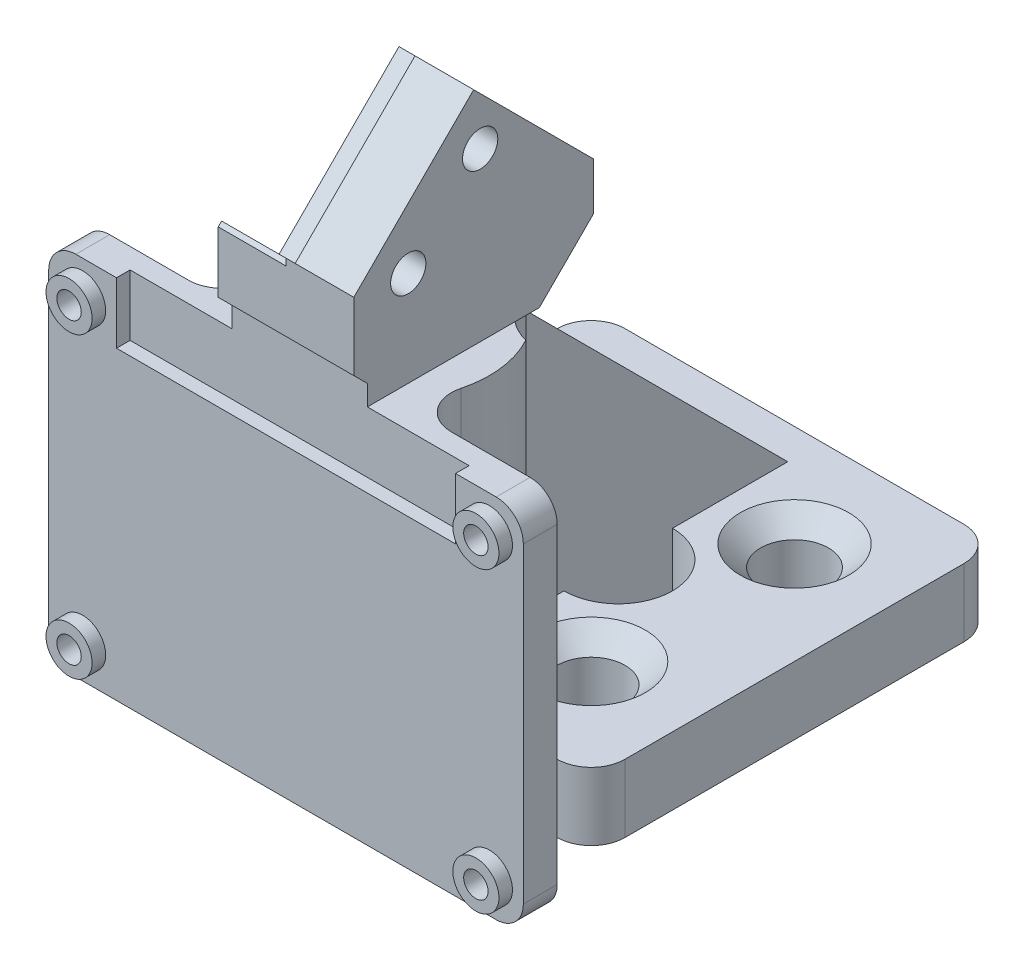
SolidWorks part; units mm, degrees
ref_plane "Front Plane" through (0, 0, 0) normal (0, 0, 1) x (1, 0, 0)
ref_plane "Top Plane" through (0, 0, 0) normal (0, 1, 0) x (1, 0, 0)
ref_plane "Right Plane" through (0, 0, 0) normal (1, 0, 0) x (0, 0, -1)
sketch "Sketch1" plane through (0, 0, 0) normal (0, 1, 0) x (1, 0, 0)
  circle A0 centre (0, 0) radius 15
  dimension "D1" = 30
extrude "Boss-Extrude1" add sketch "Sketch1" along normal blind 54
sketch "Sketch2" plane through (0, 0, 0) normal (1, 0, 0) x (0, 0, -1)
  line L0 (15, 54) -> (-15, 54) construction
  line L1 (-15, 54) -> (20.3553, 54)
  line L2 (-15, 54) -> (-15, 69)
  line L4 (20.3553, 54) -> (20.3553, 69)
  line L5 (-15, 69) -> (2.6777, 86.6777)
  line L6 (2.6777, 86.6777) -> (20.3553, 69)
  point P6 (0, 100)
  dimension "D1" = 25
  dimension "D2" = 15
  dimension "D3" = 15
  dimension "D4" = 45
  dimension "D5" = 15
extrude "Boss-Extrude2" add sketch "Sketch2" along normal mid plane 20
sketch "Sketch4" plane through (0, 42, 42) normal (0, 0.7071, 0.7071) x (1, 0, 0)
  line L0 (10, 38.1838) -> (-10, 38.1838) construction
  line L1 (-12.7, 38.1838) -> (0, 38.1838)
  line L2 (-12.7, 38.1838) -> (-12.7, 63.1838)
  line L3 (-12.7, 63.1838) -> (0, 63.1838)
  line L4 (0, 38.1838) -> (0, 63.1838)
  line L5 (10, 63.1838) -> (-10, 63.1838) construction
  dimension "D1" = 12.7
extrude "Cut-Extrude2" cut sketch "Sketch4" against normal blind 12.7
chamfer "Chamfer1" distance 1 angle 45 1 edges at (-5, 69, 15) first distance on face at (0, 61.5, 15)
sketch "Sketch5" plane through (0, 0, 0) normal (0, -1, 0) x (1, 0, 0)
  circle A0 centre (0, 0) radius 75
  dimension "D1" = 150
sketch "Sketch6" plane through (10, 0, 0) normal (1, 0, 0) x (0, 0, -1)
  line L0 (2.6777, 86.6777) -> (-15, 69) construction
  line L1 (20.3553, 69) -> (2.6777, 86.6777) construction
  line L2 (3.6323, 78.652) -> (-6.9743, 68.0454) construction
  circle A0 centre (3.6323, 78.652) radius 2.6
  circle A1 centre (-6.9743, 68.0454) radius 2.6
  dimension "D4" = 5.2
  dimension "D1" = 6.35
  dimension "D2" = 15
  dimension "D3" = 5
extrude "Cut-Extrude3" cut sketch "Sketch6" against normal through all
sketch "Sketch7" plane through (0, 0, 15) normal (0, 0, 1) x (1, 0, 0)
  line L0 (-31, 0) -> (31, 0)
  line L1 (-35, 4) -> (-35, 50)
  line L2 (-31, 54) -> (31, 54)
  line L3 (35, 4) -> (35, 50)
  line L4 (10, 54) -> (0, 54) construction
  circle A0 centre (-30, 49) radius 1.8
  circle A1 centre (30, 49) radius 1.8
  circle A2 centre (30, 5) radius 1.8
  circle A3 centre (-30, 5) radius 1.8
  arc A4 (31, 54) -> (35, 50) centre (31, 50) cw
  arc A5 (31, 0) -> (35, 4) centre (31, 4) ccw
  arc A6 (-31, 0) -> (-35, 4) centre (-31, 4) cw
  arc A7 (-35, 50) -> (-31, 54) centre (-31, 50) cw
  circle A8 centre (0, 27) radius 5 construction
  point P4 (30, 5)
  point P5 (30, 49)
  point P6 (-30, 49)
  point P7 (-30, 5)
  dimension "D1" = 3.6
  dimension "D2" = 10
  dimension "D3" = 4
  dimension "D4" = 65
  dimension "D5" = 30
  dimension "D6" = 30
  dimension "D7" = 5
  dimension "D8" = 49
  dimension "D9" = 22
  dimension "D10" = 22
  dimension "D11" = 5
extrude "Boss-Extrude4" add sketch "Sketch7" against normal blind 5
fillet "Fillet1" radius 5 2 edges at (-11.1803, 27, 10) (11.1803, 27, 10)
sketch "Sketch8" plane through (0, 0, 0) normal (0, -1, 0) x (1, 0, 0)
  line L1 (30, 0) -> (-30, 0)
  line L2 (30, 0) -> (30, -60)
  line L3 (30, -60) -> (-30, -60)
  line L4 (-30, 0) -> (-30, -60)
  point P4 (0, 0)
  dimension "D1" = 60
  dimension "D2" = 60
extrude "Boss-Extrude5" add sketch "Sketch8" against normal blind 10
sketch "Sketch9" plane through (0, 0, 0) normal (1, 0, 0) x (0, 0, -1)
  line L0 (15, 50) -> (55, 10)
  line L1 (15, 10) -> (15, 54) construction
  line L2 (60, 10) -> (0, 10) construction
  line L3 (15, 50) -> (10, 50)
  line L4 (10, 50) -> (10, 10)
  line L5 (10, 10) -> (55, 10)
  dimension "D1" = 45
  dimension "D2" = 5
  dimension "D3" = 40
extrude "Boss-Extrude6" add sketch "Sketch9" along normal mid plane 8
fillet "Fillet2" radius 5 4 edges at (-30, 5, -60) (30, 5, -60) (-30, 5, 0) (30, 5, 0)
sketch "Sketch10" plane through (0, 10, 0) normal (0, 1, 0) x (1, 0, 0)
  line L0 (-25, 60) -> (25, 60) construction
  line L1 (-15, 45) -> (15, 45) construction
  line L2 (-15, 45) -> (-15, 15) construction
  line L3 (-15, 15) -> (15, 15) construction
  line L4 (15, 45) -> (15, 15) construction
  line L5 (-15, 45) -> (15, 15) construction
  line L6 (-15, 15) -> (15, 45) construction
  circle A0 centre (15, 45) radius 5
  circle A1 centre (-15, 45) radius 5
  circle A2 centre (-15, 15) radius 5
  circle A3 centre (15, 15) radius 5
  point P8 (0, 30)
  dimension "D1" = 10
  dimension "D2" = 30
  dimension "D3" = 30
  dimension "D4" = 30
extrude "Cut-Extrude4" cut sketch "Sketch10" against normal through all
chamfer "Chamfer2" distance 8 angle 45 1 edges at (0, 54, -20.3553)
sketch "Sketch11" plane through (0, 0, 15) normal (0, 0, 1) x (1, 0, 0)
  circle A0 centre (-30, 49) radius 1.8
  circle A1 centre (30, 49) radius 1.8
  circle A2 centre (30, 5) radius 1.8
  circle A3 centre (-30, 5) radius 1.8
  circle A4 centre (-30, 49) radius 1.8 construction
extrude "Extrude-Thin1" add sketch "Sketch11" along normal blind 2 thin thin type one direction wall 1.6
sketch "Sketch12" plane through (0, 0, 15) normal (0, 0, 1) x (1, 0, 0)
  line L0 (-10, 54) -> (-31, 54) construction
  line L1 (-25, 59) -> (25, 59)
  line L2 (-25, 59) -> (-25, 45)
  line L3 (-25, 45) -> (25, 45)
  line L4 (25, 59) -> (25, 45)
  line L5 (-35, 50) -> (-35, 4) construction
  line L6 (35, 4) -> (35, 50) construction
  dimension "D1" = 9
  dimension "D2" = 10
  dimension "D3" = 10
  dimension "D4" = 14
extrude "Cut-Extrude5" cut sketch "Sketch12" against normal blind 2
chamfer "Chamfer3" distance 2 angle 45 1 edges at (0, 59, 13)
sketch "Sketch13" plane through (0, 0, 10) normal (0, 0, -1) x (-1, 0, 0)
  line L649 (-30, 45.8823) -> (-27.3, 47.4412)
  line L650 (-27.3, 47.4412) -> (-27.3, 50.5588)
  line L651 (-27.3, 50.5588) -> (-30, 52.1177)
  line L652 (-30, 52.1177) -> (-32.7, 50.5588)
  line L653 (-32.7, 50.5588) -> (-32.7, 47.4412)
  line L654 (-32.7, 47.4412) -> (-30, 45.8823)
  line L655 (30, 45.8823) -> (32.7, 47.4412)
  line L656 (32.7, 47.4412) -> (32.7, 50.5588)
  line L657 (32.7, 50.5588) -> (30, 52.1177)
  line L658 (30, 52.1177) -> (27.3, 50.5588)
  line L659 (27.3, 50.5588) -> (27.3, 47.4412)
  line L660 (27.3, 47.4412) -> (30, 45.8823)
  line L662 (27.3, 6.5588) -> (27.3, 3.4412)
  line L663 (27.3, 3.4412) -> (30, 1.8823)
  line L664 (30, 1.8823) -> (32.7, 3.4412)
  line L665 (32.7, 3.4412) -> (32.7, 6.5588)
  line L666 (32.7, 6.5588) -> (30, 8.1177)
  line L667 (30, 8.1177) -> (27.3, 6.5588)
  line L668 (-32.7, 6.5588) -> (-32.7, 3.4412)
  line L669 (-32.7, 3.4412) -> (-30, 1.8823)
  line L670 (-30, 1.8823) -> (-27.3, 3.4412)
  line L671 (-27.3, 3.4412) -> (-27.3, 6.5588)
  line L672 (-27.3, 6.5588) -> (-30, 8.1177)
  line L673 (-30, 8.1177) -> (-32.7, 6.5588)
  circle A0 centre (-30, 49) radius 2.7 construction
  circle A1 centre (30, 49) radius 2.7 construction
  circle A2 centre (30, 5) radius 2.7 construction
  circle A3 centre (-30, 5) radius 2.7 construction
  circle A4 centre (-30, 49) radius 1.8 construction
  circle A5 centre (30, 49) radius 1.8 construction
  circle A8 centre (-30, 5) radius 1.8 construction
  circle A9 centre (30, 5) radius 1.8 construction
  dimension "D1" = 5.4
  dimension "D2" = 5.4
  dimension "D3" = 5.4
  dimension "D4" = 5.4
extrude "Cut-Extrude6" cut sketch "Sketch13" against normal blind 2
sketch "Sketch14" plane through (0, 10, 0) normal (0, 1, 0) x (1, 0, 0)
  circle A0 centre (15, 15) radius 8
  circle A1 centre (-15, 15) radius 8
  circle A2 centre (15, 15) radius 5 construction
  dimension "D1" = 16
extrude "Cut-Extrude7" cut sketch "Sketch14" along normal up to surface (44 mm away) up to face at (20.8063, 54, 8.6403)
chamfer "Chamfer4" distance 3 angle 45 4 edges at (-15, 10, -40) (15, 10, -40) (15, 10, -10) (-15, 10, -10)
sketch "Sketch15" plane through (0, 10, 0) normal (0, 1, 0) x (1, 0, 0)
  line L0 (4, 14.4568) -> (4, 55) construction
  line L1 (4, 22) -> (4, 38)
  line L2 (-25, 60) -> (25, 60) construction
  arc A0 (4, 22) -> (4, 38) centre (4, 30) ccw
  dimension "D1" = 8
  dimension "D2" = 30
extrude "Cut-Extrude8" cut sketch "Sketch15" against normal through all
sketch "Sketch16" [suppressed] plane through (0, 42, 42) normal (0, 0.7071, 0.7071) x (1, 0, 0)
  line L1 (10, 63.1838) -> (-10, 63.1838)
  line L2 (10, 63.1838) -> (10, 31.1838)
  line L3 (10, 31.1838) -> (-10, 31.1838)
  line L4 (-10, 63.1838) -> (-10, 31.1838)
  dimension "D1" = 32
extrude "Cut-Extrude9" [suppressed] cut sketch "Sketch16" against normal blind 5.8
sketch "Sketch17" [suppressed] plane through (-10, 0, 0) normal (-1, 0, 0) x (0, 0, 1)
  line L0 (5.4332, 70.3643) -> (0.5542, 65.4853)
  line L1 (10.8988, 64.8988) -> (-6.7789, 82.5765) construction
  line L2 (-11.6579, 77.6974) -> (6.0197, 60.0197) construction
  line L3 (0.5542, 65.4853) -> (9.0395, 57)
  line L4 (9.0395, 57) -> (13, 57)
  line L5 (5.4332, 70.3643) -> (15.8988, 59.8988)
  line L6 (15.8988, 59.8988) -> (13, 57)
  dimension "D1" = 12
extrude "Cut-Extrude10" [suppressed] cut sketch "Sketch17" against normal through all
sketch "Sketch18" [suppressed] plane through (0, 33.0197, 33.0197) normal (0, 0.7071, 0.7071) x (1, 0, 0)
  line L0 (-6.35, 53.1838) -> (-6.35, 63.1838) construction
  line L1 (10, 63.1838) -> (6.7267, 63.1838)
  line L2 (10, 63.1838) -> (10, 53.1838)
  line L3 (10, 53.1838) -> (6.7267, 53.1838)
  line L4 (-22.7, 63.1838) -> (-22.7, 53.1838)
  line L5 (-19.4267, 53.1838) -> (-22.7, 53.1838)
  line L6 (-19.4267, 63.1838) -> (-22.7, 63.1838)
  line L7 (6.7267, 53.1838) -> (-19.4267, 53.1838) construction
  arc A4 (6.7267, 63.1838) -> (-19.4267, 63.1838) centre (-6.35, 58.1838) ccw
  arc A5 (6.7267, 53.1838) -> (-19.4267, 53.1838) centre (-6.35, 58.1838) cw
  point P8 (10, 58.1838)
  point P12 (-6.35, 63.1838)
  point P15 (-6.35, 53.1838)
  dimension "D3" = 14
  dimension "D1" = 5
  dimension "D2" = 32.7
extrude "Boss-Extrude7" [suppressed] add sketch "Sketch18" along normal up to surface (6.9 mm away) up to face at (5, 77.8388, 6.1612)
sketch "Sketch19" [suppressed] plane through (0, 20.8223, 20.8223) normal (0, -0.7071, -0.7071) x (1, 0, 0)
  line L0 (10, -46.9203) -> (10, -58.234) construction
  line L1 (-22.7, -63.1838) -> (-22.7, -53.1838) construction
  line L2 (6.25, -55.1838) -> (10, -55.1838)
  line L3 (3.25, -58.1838) -> (3.25, -63.1838)
  line L4 (6.7267, -63.1838) -> (-10, -63.1838) construction
  line L5 (10, -55.1838) -> (10, -63.1838)
  line L6 (10, -63.1838) -> (3.25, -63.1838)
  arc A0 (6.25, -55.1838) -> (3.25, -58.1838) centre (6.25, -58.1838) ccw
  point P4 (-22.7, -58.1838)
  dimension "D2" = 3
  dimension "D1" = 3.75
extrude "Cut-Extrude11" [suppressed] cut sketch "Sketch19" against normal up to surface (17.2497 mm away) up to face at (-5, 68.8586, -2.8191)
sketch "Sketch20" [suppressed] plane through (0, 33.0197, 33.0197) normal (0, -0.7071, -0.7071) x (1, 0, 0)
  line L0 (6.25, -58.1838) -> (-18.95, -58.1838) construction
  line L1 (-22.7, -63.1838) -> (-22.7, -53.1838) construction
  line L2 (10, -55.1838) -> (10, -63.1838) construction
  circle A0 centre (6.25, -58.1838) radius 1.5
  circle A1 centre (-18.95, -58.1838) radius 1.5
  point P5 (-22.7, -58.1838)
  dimension "D3" = 3
  dimension "D1" = 3.75
  dimension "D2" = 3.75
extrude "Cut-Extrude12" [suppressed] cut sketch "Sketch20" against normal through all
chamfer "Chamfer5" [suppressed] distance 7 angle 45
sketch "Sketch21" [suppressed] plane through (0, 0, 0) normal (0, 0, 1) x (1, 0, 0)
  line L0 (-10, 54) -> (-15, 54)
  line L1 (-15, 54) -> (-23.25, 62.25)
  line L2 (-23.25, 62.25) -> (-23.25, 75.5054)
  line L3 (-23.25, 75.5054) -> (-10, 75.5054)
  line L4 (-10, 54) -> (-10, 75.5054)
  line L5 (-19.4267, 75.5054) -> (-22.7, 75.5054) construction
  dimension "D1" = 45
  dimension "D2" = 13.25
extrude "Boss-Extrude8" [suppressed] add sketch "Sketch21" against normal blind 5
sketch "Sketch22" [suppressed] plane through (0, 33.0197, 33.0197) normal (0, -0.7071, -0.7071) x (1, 0, 0)
  line L0 (-23.25, -56.9259) -> (-23.25, -47.5529) construction
  line L2 (10, -63.1838) -> (10, -49.1838)
  line L3 (10, -49.1838) -> (10.7, -49.1838)
  line L4 (10.7, -63.1838) -> (10.7, -49.1838)
  line L6 (-22.7, -63.1838) -> (-22.7, -53.1838)
  line L7 (-22.7, -53.1838) -> (-23.25, -53.1838)
  line L8 (-23.25, -63.1838) -> (-23.25, -53.1838)
  line L9 (-19.4267, -63.1838) -> (-22.7, -63.1838) construction
  line L10 (-18.25, -63.1838) -> (-22.7, -63.1838)
  line L11 (-18.25, -63.1838) -> (-18.25, -65.1838)
  line L12 (-18.25, -65.1838) -> (-23.25, -65.1838)
  line L13 (-23.25, -63.1838) -> (-23.25, -65.1838)
  line L15 (10, -63.1838) -> (5.7, -63.1838)
  line L16 (10.7, -63.1838) -> (10.7, -65.1838)
  line L17 (10.7, -65.1838) -> (5.7, -65.1838)
  line L18 (5.7, -63.1838) -> (5.7, -65.1838)
  dimension "D1" = 0.7
  dimension "D2" = 14
  dimension "D3" = 2
  dimension "D4" = 5
extrude "Boss-Extrude9" [suppressed] add sketch "Sketch22" against normal up to surface (6.9 mm away) up to face at (5, 77.8388, 6.1612)
sketch "Sketch23" [suppressed] plane through (-23.25, 0, 0) normal (-1, 0, 0) x (0, 0, 1)
  line L0 (-8.1931, 83.9907) -> (-13.0721, 79.1116) construction
  line L1 (-5, 62.25) -> (0, 62.25) construction
  line L2 (-11.6579, 77.6974) -> (-6.7789, 82.5765) construction
  line L3 (-5, 71.0395) -> (-13.0721, 79.1116) construction
  line L4 (-18.0219, 84.0614) -> (-13.0721, 79.1116) construction
  line L5 (-8.1931, 83.9907) -> (0.2922, 75.5054) construction
  line L6 (-5, 65.25) -> (0, 65.25) construction
  line L7 (-5, 71.0395) -> (-5, 62.25) construction
  line L8 (0, 75.2132) -> (0, 62.25) construction
  circle A0 centre (-2.5, 65.25) radius 0.75
  circle A1 centre (-9.2184, 80.1369) radius 0.75
  dimension "D3" = 1.5
  dimension "D1" = 2
  dimension "D2" = 3
extrude "Cut-Extrude13" [suppressed] cut sketch "Sketch23" against normal blind 5
sketch "Sketch24" [suppressed] plane through (10.7, 0, 0) normal (1, 0, 0) x (0, 0, -1)
  line L0 (-0.9993, 74.7983) -> (3.8798, 69.9192) construction
  line L1 (13.0721, 79.1116) -> (1.7584, 67.7979) construction
  line L2 (-3.1206, 72.677) -> (8.1931, 83.9907) construction
  line L3 (-3.1206, 72.677) -> (1.7584, 67.7979) construction
  line L4 (6.0718, 81.8693) -> (10.9508, 76.9903) construction
  line L5 (-3.1206, 72.677) -> (8.1931, 83.9907) construction
  line L6 (13.0721, 79.1116) -> (1.7584, 67.7979) construction
  line L7 (8.1931, 83.9907) -> (13.0721, 79.1116) construction
  circle A0 centre (1.4402, 72.3588) radius 0.75
  circle A1 centre (8.5113, 79.4298) radius 0.75
  dimension "D2" = 1.5
  dimension "D1" = 3
  dimension "D3" = 3
extrude "Cut-Extrude14" [suppressed] cut sketch "Sketch24" against normal blind 5
sketch "Sketch25" [suppressed] plane through (0, 0, -20.3553) normal (0, 0, -1) x (-1, 0, 0)
  line L0 (3.375, 62) -> (3.375, 69) construction
  line L1 (-3.25, 62) -> (10, 62) construction
  line L2 (-3.25, 69) -> (10, 69) construction
  circle A0 centre (3.375, 65.5) radius 0.75
  dimension "D1" = 1.5
extrude "Cut-Extrude15" [suppressed] cut sketch "Sketch25" against normal blind 5
sketch "Sketch26" plane through (0, 33.0197, 33.0197) normal (0, 0.7071, 0.7071) x (1, 0, 0)
  line L0 (0, 60.7838) -> (0, 55.5838) construction
  line L1 (0, 45.7838) -> (0, 40.5838) construction
  line L3 (0, 38.1838) -> (0, 63.1838) construction
  circle A0 centre (-5, 58.1838) radius 2.5
  circle A1 centre (-5, 43.1838) radius 2.5
  point P5 (0, 58.1838)
  point P8 (0, 43.1838)
  dimension "D1" = 5
  dimension "D2" = 5
extrude "Cut-Extrude16" cut sketch "Sketch26" against normal blind 37
sketch "Sketch27" plane through (-10, 0, 0) normal (-1, 0, 0) x (0, 0, 1)
  line L0 (-20.3553, 62) -> (-6.1777, 47.8223)
  line L1 (-6.1777, 47.8223) -> (-27.3909, 26.6091)
  line L2 (-27.3909, 26.6091) -> (-41.5685, 40.7868)
  line L3 (-41.5685, 40.7868) -> (-20.3553, 62)
  line L4 (6.0197, 60.0197) -> (-6.1777, 47.8223) construction
  line L5 (-20.3553, 62) -> (-12.3553, 54) construction
  dimension "D1" = 30
extrude "Cut-Extrude17" cut sketch "Sketch27" against normal blind 9
chamfer "Chamfer6" distance 3 angle 45 1 edges at (-4, 29.3591, -30.1409)
sketch "Sketch29" plane through (0, 42, 42) normal (0, 0.7071, 0.7071) x (1, 0, 0)
  line L0 (10, 63.1838) -> (0, 63.1838) construction
  line L1 (0, 38.1838) -> (1.35, 38.1838)
  line L2 (0, 38.1838) -> (0, 63.1838)
  line L3 (0, 63.1838) -> (1.35, 63.1838)
  line L4 (1.35, 38.1838) -> (1.35, 63.1838)
  line L5 (10, 38.1838) -> (0, 38.1838) construction
extrude "Cut-Extrude18" cut sketch "Sketch29" against normal blind 12.7
